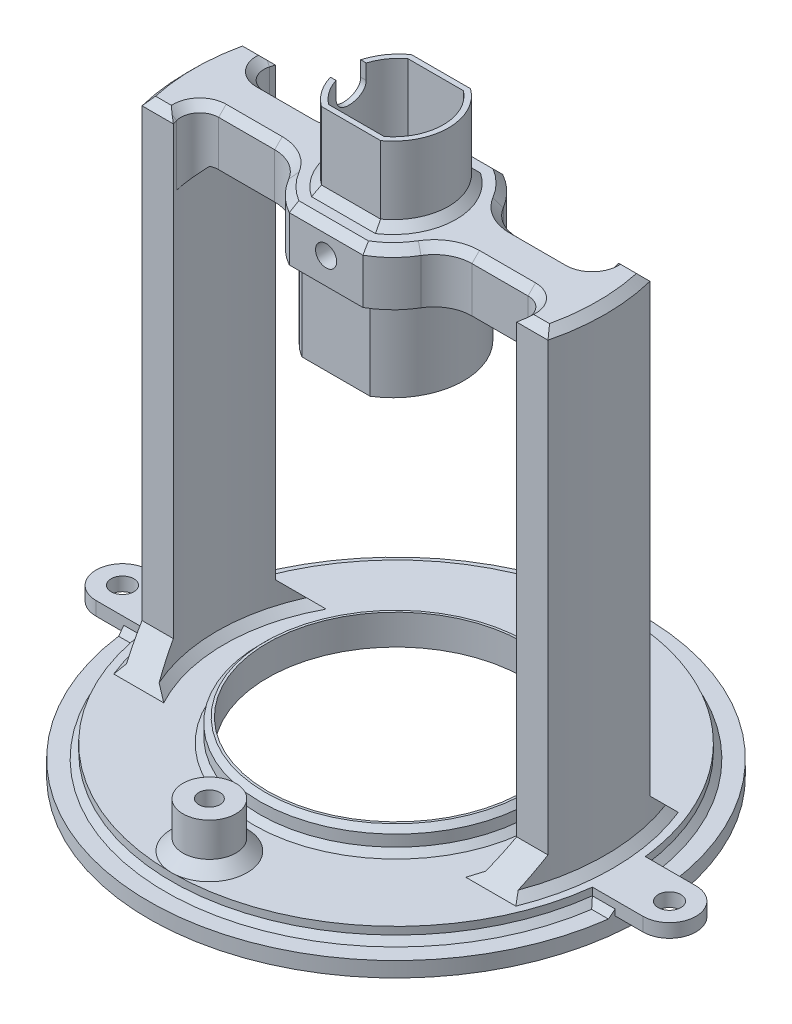
SolidWorks part; units mm, degrees
ref_plane "Front Plane" through (0, 0, 0) normal (0, 0, 1) x (1, 0, 0)
ref_plane "Top Plane" through (0, 0, 0) normal (0, 1, 0) x (1, 0, 0)
ref_plane "Right Plane" through (0, 0, 0) normal (1, 0, 0) x (0, 0, -1)
sketch "Sketch29" plane through (0, 0, 0) normal (0, 1, 0) x (1, 0, 0)
  line L0 (0, 29.0982) -> (0, -32.2718) construction
  line L1 (-4, 24.7) -> (-4, 20.3098)
  line L2 (4, 24.7) -> (4, 20.3098)
  line L3 (-7.7234, 0) -> (6.987, 0) construction
  line L4 (4, -24.7) -> (4, -20.3098)
  line L5 (-4, -24.7) -> (-4, -20.3098)
  circle A0 centre (0, 0) radius 17
  circle A2 centre (0, 0) radius 18
  circle A3 centre (0, 0) radius 19.5
  circle A4 centre (0, 0) radius 20.7
  arc A5 (4, 24.7) -> (-4, 24.7) centre (0, 24.7) ccw
  circle A6 centre (0, 24.7) radius 1.6
  circle A7 centre (0, -24.7) radius 1.6
  arc A8 (4, -24.7) -> (-4, -24.7) centre (0, -24.7) cw
  dimension "D1" = 34
  dimension "D2" = 1
  dimension "D3" = 1.5
  dimension "D4" = 1.2
  dimension "D5" = 8
  dimension "D6" = 3.2
sketch "Sketch30" plane through (0, 0, 0) normal (0, 1, 0) x (1, 0, 0)
  circle A0 centre (0, 0) radius 28.7 construction
  arc A1 (4, 24.7) -> (-4, 24.7) centre (0, 24.7) ccw construction
  circle A2 centre (0, 0) radius 29.7
  dimension "D1" = 57.4
  dimension "D2" = 1
extrude "Boss-Extrude15" add sketch "Sketch30" along normal blind 1.8
sketch "Sketch31" plane through (0, 0, 0) normal (0, -1, 0) x (1, 0, 0)
  circle A0 centre (0, 0) radius 28.7
  circle A1 centre (0, 0) radius 29.7 construction
  dimension "D1" = 1
extrude "Cut-Extrude3" cut sketch "Sketch31" against normal blind 0.8
sketch "Sketch32" plane through (0, 0, 0) normal (0, -1, 0) x (1, 0, 0)
  circle A0 centre (0, 0) radius 32.7
  circle A1 centre (0, 0) radius 28.7
  dimension "D1" = 4
extrude "Boss-Extrude16" add sketch "Sketch32" along normal blind 2
sketch "Sketch33" plane through (0, 0, 0) normal (0, 1, 0) x (1, 0, 0)
  line L0 (32.5122, -3.5) -> (29.4931, -3.5)
  line L1 (0, 10.1575) -> (0, -7.2385) construction
  line L2 (0, 29.0982) -> (0, -32.2718) construction
  line L3 (-36.2, 3.5) -> (-32.5122, 3.5)
  line L4 (-36.2, -3.5) -> (-32.5122, -3.5)
  line L7 (-32.5122, 3.5) -> (-29.4931, 3.5)
  line L8 (-32.5122, -3.5) -> (-29.4931, -3.5)
  line L9 (32.5122, 3.5) -> (29.4931, 3.5)
  line L10 (36.2, -3.5) -> (32.5122, -3.5)
  line L11 (36.2, 3.5) -> (32.5122, 3.5)
  arc A0 (-36.2, 3.5) -> (-36.2, -3.5) centre (-36.2, 0) ccw
  circle A1 centre (-36.2, 0) radius 1.5
  circle A2 centre (0, 0) radius 32.7 construction
  circle A7 centre (0, 0) radius 29.7 construction
  circle A8 centre (36.2, 0) radius 1.5
  arc A9 (36.2, 3.5) -> (36.2, -3.5) centre (36.2, 0) cw
  arc A10 (-29.4931, 3.5) -> (-29.4931, -3.5) centre (0, 0) ccw
  arc A11 (29.4931, -3.5) -> (29.4931, 3.5) centre (0, 0) ccw
  dimension "D1" = 7
  dimension "D2" = 3
extrude "Boss-Extrude17" add sketch "Sketch33" along normal up to surface (1.8 mm away) up to face at (0, 1.8, 29.7)
sketch "Sketch34" plane through (0, 1.8, 0) normal (0, 1, 0) x (1, 0, 0)
  circle A0 centre (0, 0) radius 17
  dimension "D1" = 34
extrude "Cut-Extrude4" cut sketch "Sketch34" against normal through all
sketch "Sketch35" plane through (0, 1.8, 0) normal (0, 1, 0) x (1, 0, 0)
  circle A0 centre (0, 0) radius 17
  circle A1 centre (0, 0) radius 18
  dimension "D1" = 1
  dimension "D2" = 34
extrude "Boss-Extrude18" add sketch "Sketch35" along normal blind 3
chamfer "Chamfer1" distance 1 angle 84 1 edges at (0, 0.8, -28.7) first distance on face at (0, 0.8, -28.7)
sketch "Sketch36" plane through (0, 1.8, 0) normal (0, 1, 0) x (1, 0, 0)
  circle A0 centre (0, 24.7) radius 3.5
  dimension "D1" = 7
extrude "Boss-Extrude19" add sketch "Sketch36" along normal blind 6
sketch "Sketch40" plane through (0, 7.8, 0) normal (0, 1, 0) x (1, 0, 0)
  circle A0 centre (0, 24.7) radius 1.4
  dimension "D1" = 2.8
extrude "Cut-Extrude6" cut sketch "Sketch40" against normal blind 9
mirror "Mirror1" about plane through (0, 0, 0) normal (0, 0, 1) of "Boss-Extrude19", "Cut-Extrude6"
chamfer "Chamfer2" distance 0.8 angle 45 2 edges at (0, -0.2, -28.7) (0, 1.8, 18) first distance on face at (1.1987, 0.2933, -23.9767) first distance on face at (0, 1.8, 28.2)
chamfer "Chamfer3" distance 0.7 angle 45 1 edges at (0, 4.8, 18)
sketch "Sketch42" plane through (0, 1.8, 0) normal (0, 1, 0) x (1, 0, 0)
  line L0 (-8.6268, 5.25) -> (8.8408, 5.25) construction
  line L1 (-8.6268, -5.25) -> (8.8408, -5.25) construction
  line L2 (-41.1864, 9.25) -> (47.1298, 9.25) construction
  line L3 (-36.1557, -9.25) -> (48.4574, -9.25) construction
  line L4 (-6.25, 11.6238) -> (-6.25, -11.5677) construction
  line L5 (0, 13.7269) -> (0, -14.1256) construction
  line L6 (6.25, 11.6238) -> (6.25, -11.5677) construction
  line L7 (-26.1099, 9.25) -> (-21.8203, 9.25)
  line L8 (-26.1099, -9.25) -> (-21.8203, -9.25)
  line L10 (21.8203, -9.25) -> (26.1099, -9.25)
  line L11 (21.8203, 9.25) -> (26.1099, 9.25)
  arc A0 (26.1099, -9.25) -> (26.1099, 9.25) centre (0, 0) ccw
  arc A1 (-26.1099, 9.25) -> (-26.1099, -9.25) centre (0, 0) ccw
  arc A2 (-21.8203, 9.25) -> (-21.8203, -9.25) centre (0, 0) ccw
  arc A3 (21.8203, -9.25) -> (21.8203, 9.25) centre (0, 0) ccw
  circle A4 centre (0, 0) radius 20.7 construction
  dimension "D1" = 4
  dimension "D2" = 41.4
  dimension "D3" = 3
  dimension "D4" = 5.25
  dimension "D5" = 5.25
  dimension "D6" = 4
  dimension "D7" = 4
  dimension "D8" = 6.25
extrude "Boss-Extrude20" add sketch "Sketch42" along normal blind 57
sketch "Sketch43" plane through (0, 58.8, 0) normal (0, 1, 0) x (1, 0, 0)
  line L0 (-26.1099, 9.25) -> (26.1099, 9.25)
  line L1 (-26.1099, -9.25) -> (26.1099, -9.25)
  arc A0 (26.1099, -9.25) -> (26.1099, 9.25) centre (0, 0) ccw construction
  arc A1 (-26.1099, 9.25) -> (-26.1099, -9.25) centre (0, 0) ccw construction
  arc A2 (26.1099, -9.25) -> (26.1099, 9.25) centre (0, 0) ccw
  arc A3 (-26.1099, 9.25) -> (-26.1099, -9.25) centre (0, 0) ccw
extrude "Boss-Extrude21" add sketch "Sketch43" along normal blind 7
sketch "Sketch44" plane through (0, 65.8, 0) normal (0, 1, 0) x (1, 0, 0)
  line L0 (-200008.6268, -5.25) -> (200008.8408, -5.25) construction
  line L1 (-200008.6268, 5.25) -> (200008.8408, 5.25) construction
  line L2 (6.25, 11.6238) -> (6.25, -11.5677) construction
  line L3 (0, 13.7269) -> (0, -14.1256) construction
  line L4 (-6.25, 11.6238) -> (-6.25, -11.5677) construction
  line L5 (-200008.6268, -5.25) -> (200008.8408, -5.25) construction
  line L6 (-200008.6268, 5.25) -> (200008.8408, 5.25) construction
  line L7 (6.25, 11.6238) -> (6.25, -11.5677) construction
  line L8 (0, 13.7269) -> (0, -14.1256) construction
  line L9 (-6.25, 11.6238) -> (-6.25, -11.5677) construction
  line L10 (-17.7927, 5.25) -> (16.8788, 5.25) construction
  line L11 (-17.7927, -5.25) -> (17.4705, -5.25) construction
  line L12 (-3.6817, 5.25) -> (3.6817, 5.25)
  line L13 (-3.6817, -5.25) -> (3.6817, -5.25)
  arc A0 (-3.6817, 5.25) -> (-3.6817, -5.25) centre (0.4, 0) ccw
  arc A1 (3.6817, 5.25) -> (3.6817, -5.25) centre (-0.4, 0) cw
  dimension "D1" = 13.3
  dimension "D2" = 10.5
  dimension "D3" = 12.5
extrude "Cut-Extrude7" cut sketch "Sketch44" against normal through all
sketch "Sketch45" plane through (0, 0, 9.25) normal (0, 0, 1) x (1, 0, 0)
  line L0 (0, 65.8) -> (0, 58.8) construction
  line L1 (-26.1099, 65.8) -> (26.1099, 65.8) construction
  line L2 (-21.8203, 58.8) -> (21.8203, 58.8) construction
  circle A0 centre (0, 62.3) radius 1.4
  dimension "D1" = 2.8
extrude "Cut-Extrude9" cut sketch "Sketch45" against normal blind 9
sketch "Sketch47" plane through (0, 65.8, 0) normal (0, 1, 0) x (1, 0, 0)
  line L0 (-3.6817, 5.25) -> (3.6817, 5.25)
  line L1 (-3.6817, -5.25) -> (3.6817, -5.25)
  line L2 (26.1099, 9.25) -> (-26.1099, 9.25)
  line L3 (-26.1099, -9.25) -> (26.1099, -9.25)
  line L4 (21.8203, 9.25) -> (4.8783, 9.25)
  line L5 (-21.8203, -9.25) -> (-4.8783, -9.25)
  line L8 (-20.4741, 3) -> (-13.0507, 3)
  line L9 (-25.411, 0) -> (18.4083, 0) construction
  line L10 (-20.4741, -3) -> (-13.0507, -3)
  line L11 (0, 3.5947) -> (0, -2.5789) construction
  line L12 (0, 13.7269) -> (0, -14.1256) construction
  line L13 (20.4741, -3) -> (13.0507, -3)
  line L14 (20.4741, 3) -> (13.0507, 3)
  line L15 (-4.8783, 9.25) -> (4.8783, 9.25) construction
  line L16 (-4.8783, 9.25) -> (-21.8203, 9.25)
  line L17 (4.8783, -9.25) -> (21.8203, -9.25)
  line L18 (-4.8783, -9.25) -> (4.8783, -9.25) construction
  arc A0 (3.6817, -5.25) -> (3.6817, 5.25) centre (-0.4, 0) ccw construction
  arc A1 (-3.6817, 5.25) -> (-3.6817, -5.25) centre (0.4, 0) ccw construction
  arc A2 (26.1099, -9.25) -> (26.1099, 9.25) centre (0, 0) ccw
  arc A3 (-26.1099, 9.25) -> (-26.1099, -9.25) centre (0, 0) ccw
  arc A6 (3.6817, -5.25) -> (3.6817, 5.25) centre (-0.4, 0) ccw
  arc A7 (-3.6817, 5.25) -> (-3.6817, -5.25) centre (0.4, 0) ccw
  arc A8 (4.8783, -9.25) -> (8.7534, -5.4441) centre (-0.4, 0) ccw
  arc A9 (-4.8783, 9.25) -> (-8.7534, 5.4441) centre (0.4, 0) ccw
  arc A10 (-21.8203, 9.25) -> (-21.8203, -9.25) centre (0, 0) ccw construction
  arc A11 (-21.8203, 9.25) -> (-22.8885, 6.1486) centre (0, 0) ccw
  arc A12 (21.8203, -9.25) -> (21.8203, 9.25) centre (0, 0) ccw construction
  arc A13 (21.8203, -9.25) -> (22.8885, -6.1486) centre (0, 0) ccw
  arc A14 (-22.8885, -6.1486) -> (-21.8203, -9.25) centre (0, 0) ccw
  arc A15 (22.8885, 6.1486) -> (21.8203, 9.25) centre (0, 0) ccw
  arc A16 (-8.7534, -5.4441) -> (-4.8783, -9.25) centre (0.4, 0) ccw
  arc A17 (-4.8783, 9.25) -> (-4.8783, -9.25) centre (0.4, 0) ccw construction
  arc A18 (8.7534, 5.4441) -> (4.8783, 9.25) centre (-0.4, 0) ccw
  arc A19 (4.8783, -9.25) -> (4.8783, 9.25) centre (-0.4, 0) ccw construction
  arc A20 (13.0507, 3) -> (8.7534, 5.4441) centre (13.0507, 8) cw
  arc A21 (13.0507, -3) -> (8.7534, -5.4441) centre (13.0507, -8) ccw
  arc A22 (-13.0507, -3) -> (-8.7534, -5.4441) centre (-13.0507, -8) cw
  arc A23 (-13.0507, 3) -> (-8.7534, 5.4441) centre (-13.0507, 8) ccw
  arc A24 (-22.8885, 6.1486) -> (-20.4741, 3) centre (-20.4741, 5.5) ccw
  arc A25 (-22.8885, -6.1486) -> (-20.4741, -3) centre (-20.4741, -5.5) cw
  arc A26 (22.8885, -6.1486) -> (20.4741, -3) centre (20.4741, -5.5) ccw
  arc A27 (22.8885, 6.1486) -> (20.4741, 3) centre (20.4741, 5.5) cw
  point P41 (9.8187, 3)
  point P44 (9.8187, -3)
  point P47 (-9.8187, -3)
  point P50 (-9.8187, 3)
  dimension "D2" = 5
  dimension "D4" = 5
  dimension "D3" = 3
  dimension "D1" = 0
extrude "Cut-Extrude11" cut sketch "Sketch47" against normal up to surface (7 mm away) up to face at (0, 58.8, 0)
chamfer "Chamfer5" distance 0.7 angle 45 4 edges at (0, 58.8, -5.25) (6.25, 58.8, 0) (0, 58.8, 5.25) (-6.25, 58.8, 0)
chamfer "Chamfer6" distance 2 angle 45 2 edges at (-23.7, 58.8, 0) (23.7, 58.8, 0)
chamfer "Chamfer7" distance 1.5 angle 45 2 edges at (0, 1.8, 28.2) (0, 1.8, -21.2)
chamfer "Chamfer8" distance 0.8 angle 45 6 edges at (-31.0026, 0, 3.5) (0, 0, 29.7) (31.0026, 0, 3.5) (-31.0026, 0, -3.5) (31.0026, 0, -3.5) (0, 0, -29.7)
sketch "Sketch49" plane through (0, 58.8, 0) normal (0, -1, 0) x (1, 0, 0)
  line L1 (-6, -5) -> (6, -5) construction
  line L2 (4.3181, 7.25) -> (-4.3181, 7.25)
  line L3 (-4.3181, -7.25) -> (4.3181, -7.25)
  line L4 (-4.5214, -7.95) -> (4.5214, -7.95)
  line L5 (4.5214, 7.95) -> (-4.5214, 7.95)
  line L6 (-4.5214, -7.95) -> (4.5214, -7.95)
  line L7 (4.5214, 7.95) -> (-4.5214, 7.95)
  line L8 (-6, -5) -> (-6, 5) construction
  line L9 (-6, 5) -> (6, 5) construction
  line L10 (6, -5) -> (6, 5) construction
  line L11 (-6, -5) -> (6, 5) construction
  line L12 (-6, 5) -> (6, -5) construction
  arc A2 (-4.3181, 7.25) -> (-4.3181, -7.25) centre (0.4, 0) ccw
  arc A3 (4.3181, -7.25) -> (4.3181, 7.25) centre (-0.4, 0) ccw
  arc A4 (4.5214, -7.95) -> (4.5214, 7.95) centre (-0.4, 0) ccw
  arc A5 (-4.5214, 7.95) -> (-4.5214, -7.95) centre (0.4, 0) ccw
  arc A6 (4.5214, -7.95) -> (4.5214, 7.95) centre (-0.4, 0) ccw
  arc A7 (-4.5214, 7.95) -> (-4.5214, -7.95) centre (0.4, 0) ccw
  point P6 (0, 0)
  dimension "D3" = 12
  dimension "D4" = 10
  dimension "D1" = 2
  dimension "D2" = 0.7
extrude "Boss-Extrude22" add sketch "Sketch49" along normal blind 11
sketch "Sketch50" plane through (0, 65.8, 0) normal (0, 1, 0) x (1, 0, 0)
  line L6 (-3.6817, -5.25) -> (3.6817, -5.25) construction
  line L7 (3.6817, 5.25) -> (-3.6817, 5.25) construction
  line L8 (-3.6817, -5.25) -> (3.6817, -5.25)
  line L9 (3.6817, 5.25) -> (-3.6817, 5.25)
  line L10 (3.9151, 5.95) -> (-3.9151, 5.95)
  line L11 (-3.9151, -5.95) -> (3.9151, -5.95)
  arc A6 (3.6817, -5.25) -> (3.6817, 5.25) centre (-0.4, 0) ccw construction
  arc A7 (-3.6817, 5.25) -> (-3.6817, -5.25) centre (0.4, 0) ccw construction
  arc A8 (3.6817, -5.25) -> (3.6817, 5.25) centre (-0.4, 0) ccw
  arc A9 (-3.6817, 5.25) -> (-3.6817, -5.25) centre (0.4, 0) ccw
  arc A10 (3.9151, -5.95) -> (3.9151, 5.95) centre (-0.4, 0) ccw
  arc A11 (-3.9151, 5.95) -> (-3.9151, -5.95) centre (0.4, 0) ccw
  dimension "D1" = 0.7
extrude "Boss-Extrude23" add sketch "Sketch50" along normal blind 10
sketch "Sketch51" plane through (0, 0, 0) normal (1, 0, 0) x (0, 0, -1)
  line L0 (0, 75.8) -> (0, 56.9627) construction
  line L1 (5.95, 75.8) -> (-5.95, 75.8) construction
  line L2 (-2, 73.8) -> (-2, 75.8)
  line L3 (2, 73.8) -> (2, 75.8)
  line L4 (-2, 75.8) -> (2, 75.8)
  arc A0 (-2, 73.8) -> (2, 73.8) centre (0, 73.8) ccw
  dimension "D1" = 4
extrude "Cut-Extrude12" cut sketch "Sketch51" against normal blind 17
sketch "Sketch55" plane through (0, 65.8, 0) normal (0, 1, 0) x (1, 0, 0)
  line L1 (21.8203, -9.25) -> (26.1099, -9.25) construction
  line L2 (22.7184, 6.75) -> (26.865, 6.75)
  line L6 (26.1099, 9.25) -> (21.8203, 9.25) construction
  line L7 (-26.1099, -9.25) -> (-21.8203, -9.25) construction
  line L8 (-21.8203, 9.25) -> (-26.1099, 9.25) construction
  line L9 (21.8203, -9.25) -> (26.1099, -9.25)
  line L10 (26.1099, 9.25) -> (21.8203, 9.25)
  line L11 (-26.1099, -9.25) -> (-21.8203, -9.25)
  line L12 (-21.8203, 9.25) -> (-26.1099, 9.25)
  line L13 (-26.865, 6.75) -> (-22.7184, 6.75)
  line L14 (-4.1314, 0) -> (3.818, 0) construction
  line L15 (-26.865, -6.75) -> (-22.7184, -6.75)
  line L16 (22.7184, -6.75) -> (26.865, -6.75)
  arc A4 (26.1099, -9.25) -> (26.1099, 9.25) centre (0, 0) ccw construction
  arc A5 (-26.1099, 9.25) -> (-26.1099, -9.25) centre (0, 0) ccw construction
  arc A6 (26.1099, -9.25) -> (26.865, -6.75) centre (0, 0) ccw
  arc A7 (-26.1099, 9.25) -> (-26.865, 6.75) centre (0, 0) ccw
  arc A8 (21.8203, -9.25) -> (21.8203, 9.25) centre (0, 0) ccw construction
  arc A9 (-21.8203, 9.25) -> (-21.8203, -9.25) centre (0, 0) ccw construction
  arc A10 (21.8203, -9.25) -> (22.7184, -6.75) centre (0, 0) ccw
  arc A11 (-21.8203, 9.25) -> (-22.7184, 6.75) centre (0, 0) ccw
  arc A12 (-22.7184, -6.75) -> (-21.8203, -9.25) centre (0, 0) ccw
  arc A13 (-26.865, -6.75) -> (-26.1099, -9.25) centre (0, 0) ccw
  arc A14 (26.865, 6.75) -> (26.1099, 9.25) centre (0, 0) ccw
  arc A15 (22.7184, 6.75) -> (21.8203, 9.25) centre (0, 0) ccw
  dimension "D1" = 2.5
extrude "Cut-Extrude14" cut sketch "Sketch55" against normal up to surface (64 mm away) up to face at (0, 1.8, 18.8)
chamfer "Chamfer9" distance 0.8 angle 45 4 edges at (0, 58.8, 7.95) (8.95, 58.8, 0) (0, 58.8, -7.95) (-8.95, 58.8, 0)
chamfer "Chamfer10" distance 4 angle 45 4 edges at (24.7917, 1.8, -6.75) (24.7917, 1.8, 6.75) (-24.7917, 1.8, -6.75) (-24.7917, 1.8, 6.75)
chamfer "Chamfer11" distance 1 angle 45 32 edges at (27.7, 1.8, 0) (23.7, 1.8, 0) (-23.7, 1.8, 0) (-27.7, 1.8, 0) (-6.95, 65.8, 0) (0, 65.8, 5.95) (6.95, 65.8, 0) (0, 65.8, -5.95) (-27.7, 65.8, 0) (-24.7917, 65.8, -6.75) (-22.458, 65.8, -3.9787) (-16.7624, 65.8, -3) (-10.5789, 65.8, -3.6538) (-7.0625, 65.8, -7.5982) (0, 65.8, -9.25) (7.0625, 65.8, -7.5982) (10.5789, 65.8, -3.6538) (16.7624, 65.8, -3) (22.458, 65.8, -3.9787) (24.7917, 65.8, -6.75) (27.7, 65.8, 0) (24.7917, 65.8, 6.75) (22.458, 65.8, 3.9787) (16.7624, 65.8, 3) (10.5789, 65.8, 3.6538) (7.0625, 65.8, 7.5982) (0, 65.8, 9.25) (-7.0625, 65.8, 7.5982) (-10.5789, 65.8, 3.6538) (-16.7624, 65.8, 3) (-22.458, 65.8, 3.9787) (-24.7917, 65.8, 6.75)
